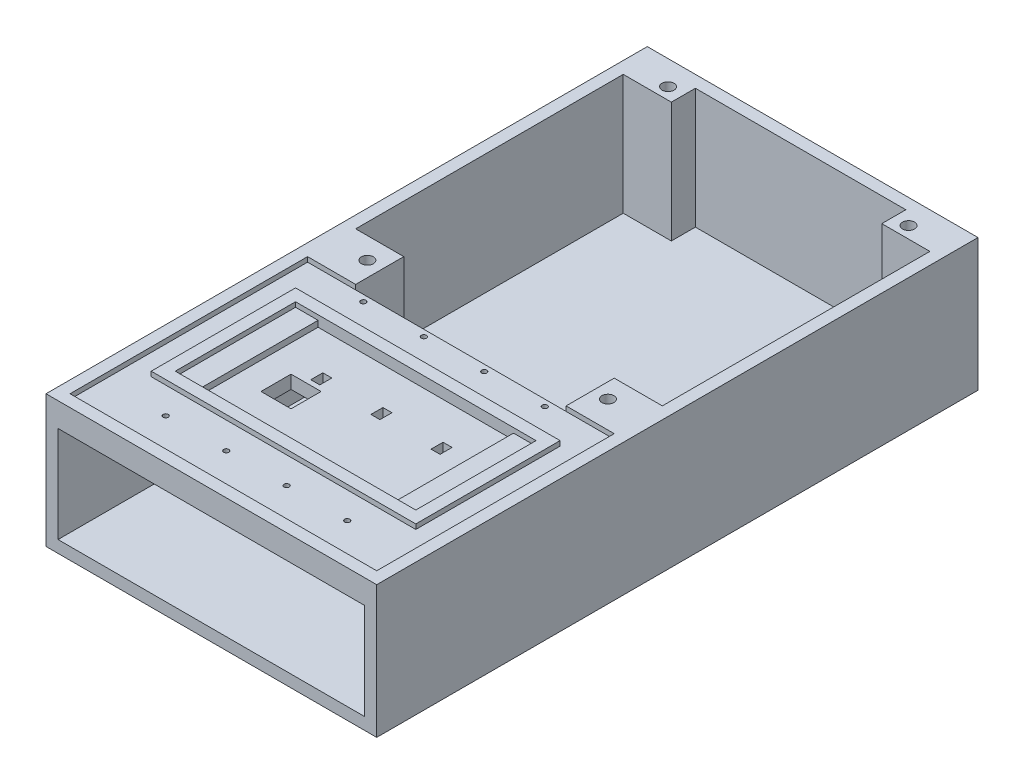
SolidWorks part; units mm, degrees
ref_plane "Front Plane" through (0, 0, 0) normal (0, 0, 1) x (1, 0, 0)
ref_plane "Top Plane" through (0, 0, 0) normal (0, 1, 0) x (1, 0, 0)
ref_plane "Right Plane" through (0, 0, 0) normal (1, 0, 0) x (0, 0, -1)
sketch "Sketch1" plane through (0, 0, 0) normal (0, 1, 0) x (1, 0, 0)
  line L1 (0, 0) -> (139.7, 0)
  line L2 (0, 0) -> (0, 254)
  line L3 (0, 254) -> (139.7, 254)
  line L4 (139.7, 0) -> (139.7, 254)
  dimension "D1" = 254
  dimension "D2" = 139.7
extrude "Base" add sketch "Sketch1" along normal blind 5.08
sketch "Sketch2" plane through (0, 5.08, 0) normal (0, 1, 0) x (1, 0, 0)
  line L1 (0, 254) -> (139.7, 254)
  line L2 (0, 254) -> (0, 0)
  line L3 (0, 0) -> (139.7, 0)
  line L4 (139.7, 254) -> (139.7, 0)
  line L5 (5.08, 248.92) -> (134.62, 248.92)
  line L6 (5.08, 248.92) -> (5.08, 5.08)
  line L7 (5.08, 5.08) -> (134.62, 5.08)
  line L8 (134.62, 248.92) -> (134.62, 5.08)
  line M9 (0, 254) -> (0, 0)
  line M10 (0, 0) -> (139.7, 0)
  line M11 (139.7, 0) -> (139.7, 254)
  line M12 (139.7, 254) -> (0, 254)
  dimension "D1" = 5.08
  dimension "D2" = 5.08
  dimension "D3" = 5.08
  dimension "D4" = 5.08
extrude "Walls" add sketch "Sketch2" along normal blind 50.8 contours L5 L8 L7 L6 M12 M9 M10 M11 region at (69.85, 5.08, -251.1012)
sketch "Sketch3" [suppressed] plane through (0, 55.88, 0) normal (0, 1, 0) x (1, 0, 0)
  line L1 (5.08, 248.92) -> (134.62, 248.92)
  line L2 (5.08, 248.92) -> (5.08, 5.08)
  line L3 (5.08, 5.08) -> (134.62, 5.08)
  line L4 (134.62, 248.92) -> (134.62, 5.08)
  line L5 (2.54, 251.46) -> (137.16, 251.46)
  line L6 (2.54, 251.46) -> (2.54, 2.54)
  line L7 (2.54, 2.54) -> (137.16, 2.54)
  line L8 (137.16, 251.46) -> (137.16, 2.54)
  dimension "D1" = 2.54
  dimension "D2" = 2.54
  dimension "D3" = 2.54
  dimension "D4" = 2.54
sketch "Sketch5" plane through (0, 5.08, 0) normal (0, 1, 0) x (1, 0, 0)
  line L0 (5.08, 5.08) -> (5.08, 248.92) construction
  line L1 (5.08, 105.41) -> (134.62, 105.41)
  line L2 (5.08, 105.41) -> (5.08, 16.51)
  line L3 (5.08, 16.51) -> (134.62, 16.51)
  line L4 (134.62, 105.41) -> (134.62, 16.51)
  line L6 (134.62, 248.92) -> (134.62, 5.08) construction
  point P8 (134.62, 60.96)
  dimension "D1" = 60.96
  dimension "D2" = 88.9
extrude "Button Support" add sketch "Sketch5" along normal blind 48.768
ref_plane "Plane1" through (0, 0, -60.96) normal (0, 0, 1) x (1, 0, 0)
sketch "Sketch6" plane through (0, 53.848, 0) normal (0, 1, 0) x (1, 0, 0)
  line L0 (0, 0) -> (139.7, 0) construction
  line L1 (19.05, 86.36) -> (120.65, 86.36)
  line L2 (19.05, 86.36) -> (19.05, 35.56)
  line L3 (19.05, 35.56) -> (120.65, 35.56)
  line L4 (120.65, 86.36) -> (120.65, 35.56)
  line L5 (125.73, 91.44) -> (13.97, 91.44)
  line L6 (125.73, 91.44) -> (125.73, 30.48)
  line L7 (125.73, 30.48) -> (13.97, 30.48)
  line L8 (13.97, 91.44) -> (13.97, 30.48)
  line L9 (134.62, 105.41) -> (5.08, 105.41) construction
  point P8 (69.85, 91.44)
  point P9 (69.85, 86.36)
  point P10 (120.65, 60.96)
  point P11 (125.73, 60.96)
  point P16 (69.85, 105.41)
  dimension "D1" = 50.8
  dimension "D2" = 60.96
  dimension "D3" = 101.6
  dimension "D4" = 5.08
  dimension "D5" = 5.08
extrude "Boss-Extrude4" add sketch "Sketch6" along normal blind 2.032
sketch "Sketch7" plane through (0, 53.848, 0) normal (0, 1, 0) x (1, 0, 0)
  line L0 (19.05, 35.56) -> (120.65, 35.56) construction
  line L1 (28.575, 35.56) -> (111.125, 35.56)
  line L2 (28.575, 35.56) -> (28.575, 86.36)
  line L3 (28.575, 86.36) -> (111.125, 86.36)
  line L4 (111.125, 35.56) -> (111.125, 86.36)
  line L5 (120.65, 86.36) -> (19.05, 86.36) construction
  point P8 (69.85, 86.36)
  point P9 (69.85, 35.56)
  dimension "D1" = 82.55
  dimension "D2" = 50.8
extrude "Force Sensor Cutout" cut sketch "Sketch7" against normal blind 2.54
sketch "Sketch4" plane through (0, 0, 0) normal (0, 0, 1) x (1, 0, 0)
  line L0 (0, 0) -> (139.7, 0) construction
  line L1 (5.08, 45.72) -> (134.62, 45.72)
  line L2 (5.08, 45.72) -> (5.08, 5.08)
  line L3 (5.08, 5.08) -> (134.62, 5.08)
  line L4 (134.62, 45.72) -> (134.62, 5.08)
  line L5 (0, 55.88) -> (0, 0) construction
  line L6 (139.7, 55.88) -> (139.7, 0) construction
  line L7 (0, 55.88) -> (139.7, 55.88) construction
  dimension "D1" = 5.08
  dimension "D2" = 5.08
  dimension "D3" = 5.08
  dimension "D4" = 10.16
extrude "Bottom Cut" cut sketch "Sketch4" against normal blind 139.7
sketch "Sketch8" plane through (0, 51.308, 0) normal (0, 1, 0) x (1, 0, 0)
  line L0 (120.65, 86.36) -> (19.05, 86.36) construction
  line L1 (71.628, 65.623) -> (75.438, 65.623)
  line L2 (71.628, 65.623) -> (71.628, 70.703)
  line L3 (71.628, 70.703) -> (75.438, 70.703)
  line L4 (75.438, 65.623) -> (75.438, 70.703)
  line L5 (120.65, 35.56) -> (120.65, 86.36) construction
  line L6 (97.028, 65.623) -> (97.028, 70.703)
  line L7 (97.028, 65.623) -> (100.838, 65.623)
  line L8 (100.838, 65.623) -> (100.838, 70.703)
  line L9 (97.028, 70.703) -> (100.838, 70.703)
  line L10 (46.228, 65.623) -> (46.228, 70.703)
  line L11 (46.228, 65.623) -> (50.038, 65.623)
  line L12 (50.038, 65.623) -> (50.038, 70.703)
  line L13 (46.228, 70.703) -> (50.038, 70.703)
  dimension "D1" = 15.657
  dimension "D2" = 45.212
  dimension "D3" = 3.81
  dimension "D4" = 5.08
  dimension "D5" = 2
  dimension "D6" = 2
extrude "Haptic Wire Holes" cut sketch "Sketch8" against normal up to surface (5.588 mm away) up to face at (69.85, 45.72, -60.96)
sketch "Sketch9" plane through (0, 51.308, 0) normal (0, 1, 0) x (1, 0, 0)
  line L0 (120.65, 86.36) -> (19.05, 86.36) construction
  line L1 (52.705, 63.5) -> (40.005, 63.5)
  line L2 (52.705, 63.5) -> (52.705, 50.8)
  line L3 (52.705, 50.8) -> (40.005, 50.8)
  line L4 (40.005, 63.5) -> (40.005, 50.8)
  line L5 (28.575, 86.36) -> (28.575, 35.56) construction
  dimension "D1" = 12.7
  dimension "D2" = 12.7
  dimension "D3" = 22.86
  dimension "D4" = 11.43
extrude "Force Sensor Hole" cut sketch "Sketch9" against normal up to surface (5.588 mm away) up to face at (48.133, 45.72, -68.163)
sketch "Sketch10" plane through (0, 53.848, 0) normal (0, 1, 0) x (1, 0, 0)
  line L0 (5.08, 16.51) -> (134.62, 16.51) construction
  line L1 (134.62, 105.41) -> (134.62, 16.51) construction
  line L2 (-4.4704, 60.96) -> (4.4704, 60.96) construction
  circle A0 centre (108.0186, 19.2295) radius 1.0795
  circle A4 centre (82.4261, 19.2295) radius 1.0795
  circle A5 centre (56.9186, 19.2295) radius 1.0795
  circle A6 centre (31.3261, 19.2295) radius 1.0795
  circle A7 centre (31.3261, 102.6905) radius 1.0795
  circle A8 centre (56.9186, 102.6905) radius 1.0795
  circle A9 centre (82.4261, 102.6905) radius 1.0795
  circle A10 centre (108.0186, 102.6905) radius 1.0795
  dimension "D1" = 2.159
  dimension "D2" = 2.7195
  dimension "D3" = 26.6014
  dimension "D5" = 25.5925
  dimension "D6" = 25.5075
  dimension "D4" = 25.5925
extrude "NeoPixel Holes" cut sketch "Sketch10" against normal up to surface (8.128 mm away) up to face at (46.355, 45.72, -57.15)
sketch "Sketch11" plane through (0, 0, -16.51) normal (0, 0, 1) x (1, 0, 0)
  line L1 (5.08, 53.848) -> (134.62, 53.848)
  line L2 (5.08, 53.848) -> (5.08, 45.72)
  line L3 (5.08, 45.72) -> (134.62, 45.72)
  line L4 (134.62, 53.848) -> (134.62, 45.72)
extrude "Boss-Extrude5" add sketch "Sketch11" along normal up to next
sketch "Sketch12" plane through (0, 5.08, 0) normal (0, 1, 0) x (1, 0, 0)
  line L0 (139.7, 254) -> (0, 254) construction
  line L1 (134.62, 248.92) -> (114.3, 248.92)
  line L2 (134.62, 248.92) -> (134.62, 238.76)
  line L3 (134.62, 238.76) -> (114.3, 238.76)
  line L4 (114.3, 248.92) -> (114.3, 238.76)
  line L5 (139.7, 0) -> (139.7, 254) construction
  line L7 (5.08, 248.92) -> (25.4, 248.92)
  line L8 (5.08, 248.92) -> (5.08, 238.76)
  line L9 (5.08, 238.76) -> (25.4, 238.76)
  line L10 (25.4, 248.92) -> (25.4, 238.76)
  line L11 (134.62, 105.41) -> (114.3, 105.41)
  line L12 (134.62, 105.41) -> (134.62, 125.73)
  line L13 (134.62, 125.73) -> (114.3, 125.73)
  line L14 (114.3, 105.41) -> (114.3, 125.73)
  line L15 (5.08, 105.41) -> (25.4, 105.41)
  line L16 (5.08, 105.41) -> (5.08, 125.73)
  line L17 (5.08, 125.73) -> (25.4, 125.73)
  line L18 (25.4, 105.41) -> (25.4, 125.73)
  dimension "D1" = 15.24
  dimension "D2" = 25.4
  dimension "D3" = 20.32
extrude "Mounting Struts" add sketch "Sketch12" along normal up to surface (50.8 mm away) up to face at (69.85, 55.88, -127)
sketch "Sketch13" plane through (0, 55.88, 0) normal (0, 1, 0) x (1, 0, 0)
  line L0 (139.7, 254) -> (0, 254) construction
  line L1 (139.7, 0) -> (139.7, 254) construction
  circle A0 centre (120.65, 243.713) radius 2.54
  circle A1 centre (19.05, 243.713) radius 2.54
  circle A2 centre (120.65, 116.713) radius 2.54
  circle A3 centre (19.05, 116.713) radius 2.54
  point P12 (0, 0)
  point P13 (0, 0)
  point P14 (0, 0)
  point P15 (0, 0)
  dimension "D1" = 5.08
  dimension "D2" = 10.287
  dimension "D3" = 19.05
  dimension "D4" = 101.6
  dimension "D5" = 127
extrude "Panel Mounting Holes" cut sketch "Sketch13" against normal blind 12.7
